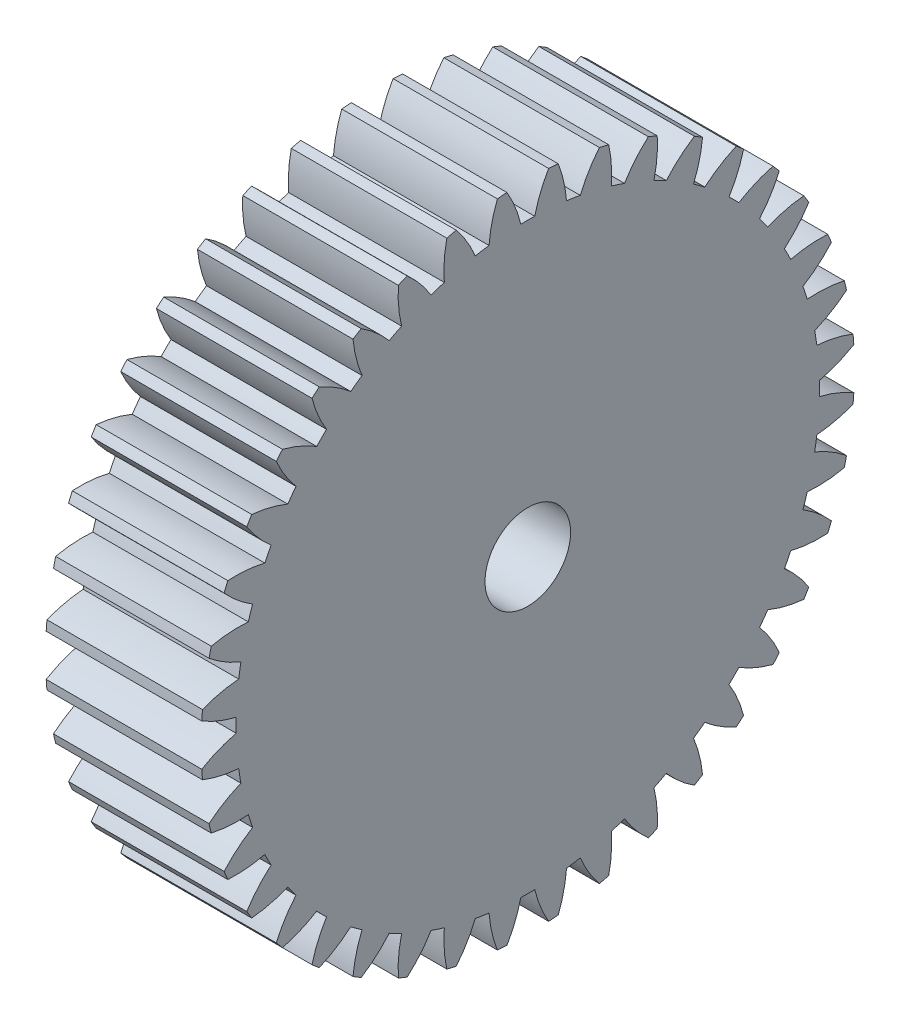
SolidWorks part; units mm, degrees
ref_plane "Front Plane" through (0, 0, 0) normal (0, 0, 1) x (1, 0, 0)
ref_plane "Top Plane" through (0, 0, 0) normal (0, 1, 0) x (1, 0, 0)
ref_plane "Right Plane" through (0, 0, 0) normal (1, 0, 0) x (0, 0, -1)
ref_plane "Plane1" through (-1.595, 0, 0) normal (1, 0, 0) x (0, 0, -1)
sketch "Sketch1" plane through (-1.595, 0, 0) normal (1, 0, 0) x (0, 0, -1)
  circle A0 centre (-8.0381, 6.9342) radius 0.4
  arc A1 (-16.421, 7.4699) -> (-15.535, 7.1132) centre (-14.7963, 10.2268) ccw
  arc A2 (-15.535, 7.1132) -> (-15.535, 6.7552) centre (-8.0381, 6.9342) ccw
  arc A3 (-15.535, 6.7552) -> (-16.421, 6.3985) centre (-14.7963, 3.6417) ccw
  arc A4 (-16.421, 6.3985) -> (-16.4016, 6.152) centre (-8.0381, 6.9342) ccw
  arc A5 (-16.4016, 6.152) -> (-15.4707, 5.9382) centre (-15.2282, 9.129) ccw
  arc A6 (-15.4707, 5.9382) -> (-15.4147, 5.5847) centre (-8.0381, 6.9342) ccw
  arc A7 (-15.4147, 5.5847) -> (-16.234, 5.0937) centre (-14.198, 2.625) ccw
  arc A8 (-16.234, 5.0937) -> (-16.1763, 4.8533) centre (-8.0381, 6.9342) ccw
  arc A9 (-16.1763, 4.8533) -> (-15.2234, 4.7878) centre (-15.483, 7.9773) ccw
  arc A10 (-15.2234, 4.7878) -> (-15.1128, 4.4473) centre (-8.0381, 6.9342) ccw
  arc A11 (-15.1128, 4.4473) -> (-15.8452, 3.8343) centre (-13.4481, 1.7144) ccw
  arc A12 (-15.8452, 3.8343) -> (-15.7506, 3.6058) centre (-8.0381, 6.9342) ccw
  arc A13 (-15.7506, 3.6058) -> (-14.7992, 3.6902) centre (-15.5545, 6.7998) ccw
  arc A14 (-14.7992, 3.6902) -> (-14.6366, 3.3712) centre (-8.0381, 6.9342) ccw
  arc A15 (-14.6366, 3.3712) -> (-15.2641, 2.6511) centre (-12.5649, 0.9324) ccw
  arc A16 (-15.2641, 2.6511) -> (-15.1349, 2.4403) centre (-8.0381, 6.9342) ccw
  arc A17 (-15.1349, 2.4403) -> (-14.2084, 2.6725) centre (-15.4409, 5.6256) ccw
  arc A18 (-14.2084, 2.6725) -> (-13.998, 2.3829) centre (-8.0381, 6.9342) ccw
  arc A19 (-13.998, 2.3829) -> (-14.5052, 1.5735) centre (-11.5703, 0.2981) ccw
  arc A20 (-14.5052, 1.5735) -> (-14.3446, 1.3854) centre (-8.0381, 6.9342) ccw
  arc A21 (-14.3446, 1.3854) -> (-13.4658, 1.7597) centre (-15.1451, 4.4837) ccw
  arc A22 (-13.4658, 1.7597) -> (-13.2127, 1.5066) centre (-8.0381, 6.9342) ccw
  arc A23 (-13.2127, 1.5066) -> (-13.5869, 0.6278) centre (-10.4887, -0.1727) ccw
  arc A24 (-13.5869, 0.6278) -> (-13.3989, 0.4672) centre (-8.0381, 6.9342) ccw
  arc A25 (-13.3989, 0.4672) -> (-12.5895, 0.9743) centre (-14.6742, 3.4021) ccw
  arc A26 (-12.5895, 0.9743) -> (-12.2999, 0.7639) centre (-8.0381, 6.9342) ccw
  arc A27 (-12.2999, 0.7639) -> (-12.5321, -0.1626) centre (-9.3467, -0.4686) ccw
  arc A28 (-12.5321, -0.1626) -> (-12.3212, -0.2918) centre (-8.0381, 6.9342) ccw
  arc A29 (-12.3212, -0.2918) -> (-11.6011, 0.3357) centre (-14.04, 2.4075) ccw
  arc A30 (-11.6011, 0.3357) -> (-11.2822, 0.1732) centre (-8.0381, 6.9342) ccw
  arc A31 (-11.2822, 0.1732) -> (-11.3666, -0.7782) centre (-8.1726, -0.5821) ccw
  arc A32 (-11.3666, -0.7782) -> (-11.1381, -0.8728) centre (-8.0381, 6.9342) ccw
  arc A33 (-11.1381, -0.8728) -> (-10.525, -0.1404) centre (-13.2579, 1.5243) ccw
  arc A34 (-10.525, -0.1404) -> (-10.1846, -0.251) centre (-8.0381, 6.9342) ccw
  arc A35 (-10.1846, -0.251) -> (-10.1191, -1.2039) centre (-6.9951, -0.5106) ccw
  arc A36 (-10.1191, -1.2039) -> (-9.8786, -1.2617) centre (-8.0381, 6.9342) ccw
  arc A37 (-9.8786, -1.2617) -> (-9.3877, -0.4423) centre (-12.3474, 0.7744) ccw
  arc A38 (-9.3877, -0.4423) -> (-9.0341, -0.4984) centre (-8.0381, 6.9342) ccw
  arc A39 (-9.0341, -0.4984) -> (-8.8204, -1.4293) centre (-5.8433, -0.2558) ccw
  arc A40 (-8.8204, -1.4293) -> (-8.5739, -1.4487) centre (-8.0381, 6.9342) ccw
  arc A41 (-8.5739, -1.4487) -> (-8.2171, -0.5626) centre (-11.3307, 0.1761) ccw
  arc A42 (-8.2171, -0.5626) -> (-7.8591, -0.5626) centre (-8.0381, 6.9342) ccw
  arc A43 (-7.8591, -0.5626) -> (-7.5024, -1.4487) centre (-4.7456, 0.1761) ccw
  arc A44 (-7.5024, -1.4487) -> (-7.2559, -1.4293) centre (-8.0381, 6.9342) ccw
  arc A45 (-7.2559, -1.4293) -> (-7.0422, -0.4984) centre (-10.233, -0.2558) ccw
  arc A46 (-7.0422, -0.4984) -> (-6.6886, -0.4423) centre (-8.0381, 6.9342) ccw
  arc A47 (-6.6886, -0.4423) -> (-6.1976, -1.2617) centre (-3.7289, 0.7744) ccw
  arc A48 (-6.1976, -1.2617) -> (-5.9572, -1.2039) centre (-8.0381, 6.9342) ccw
  arc A49 (-5.9572, -1.2039) -> (-5.8917, -0.251) centre (-9.0812, -0.5106) ccw
  arc A50 (-5.8917, -0.251) -> (-5.5512, -0.1404) centre (-8.0381, 6.9342) ccw
  arc A51 (-5.5512, -0.1404) -> (-4.9382, -0.8728) centre (-2.8184, 1.5243) ccw
  arc A52 (-4.9382, -0.8728) -> (-4.7097, -0.7782) centre (-8.0381, 6.9342) ccw
  arc A53 (-4.7097, -0.7782) -> (-4.7941, 0.1732) centre (-7.9037, -0.5821) ccw
  arc A54 (-4.7941, 0.1732) -> (-4.4752, 0.3357) centre (-8.0381, 6.9342) ccw
  arc A55 (-4.4752, 0.3357) -> (-3.7551, -0.2918) centre (-2.0363, 2.4075) ccw
  arc A56 (-3.7551, -0.2918) -> (-3.5442, -0.1626) centre (-8.0381, 6.9342) ccw
  arc A57 (-3.5442, -0.1626) -> (-3.7764, 0.7639) centre (-6.7296, -0.4686) ccw
  arc A58 (-3.7764, 0.7639) -> (-3.4868, 0.9743) centre (-8.0381, 6.9342) ccw
  arc A59 (-3.4868, 0.9743) -> (-2.6774, 0.4672) centre (-1.4021, 3.4021) ccw
  arc A60 (-2.6774, 0.4672) -> (-2.4894, 0.6278) centre (-8.0381, 6.9342) ccw
  arc A61 (-2.4894, 0.6278) -> (-2.8636, 1.5066) centre (-5.5876, -0.1727) ccw
  arc A62 (-2.8636, 1.5066) -> (-2.6105, 1.7597) centre (-8.0381, 6.9342) ccw
  arc A63 (-2.6105, 1.7597) -> (-1.7317, 1.3854) centre (-0.9312, 4.4837) ccw
  arc A64 (-1.7317, 1.3854) -> (-1.5711, 1.5735) centre (-8.0381, 6.9342) ccw
  arc A65 (-1.5711, 1.5735) -> (-2.0783, 2.3829) centre (-4.506, 0.2981) ccw
  arc A66 (-2.0783, 2.3829) -> (-1.8678, 2.6725) centre (-8.0381, 6.9342) ccw
  arc A67 (-1.8678, 2.6725) -> (-0.9413, 2.4403) centre (-0.6354, 5.6256) ccw
  arc A68 (-0.9413, 2.4403) -> (-0.8121, 2.6511) centre (-8.0381, 6.9342) ccw
  arc A69 (-0.8121, 2.6511) -> (-1.4397, 3.3712) centre (-3.5114, 0.9324) ccw
  arc A70 (-1.4397, 3.3712) -> (-1.2771, 3.6902) centre (-8.0381, 6.9342) ccw
  arc A71 (-1.2771, 3.6902) -> (-0.3257, 3.6058) centre (-0.5218, 6.7998) ccw
  arc A72 (-0.3257, 3.6058) -> (-0.2311, 3.8343) centre (-8.0381, 6.9342) ccw
  arc A73 (-0.2311, 3.8343) -> (-0.9635, 4.4473) centre (-2.6282, 1.7144) ccw
  arc A74 (-0.9635, 4.4473) -> (-0.8529, 4.7878) centre (-8.0381, 6.9342) ccw
  arc A75 (-0.8529, 4.7878) -> (0.1, 4.8533) centre (-0.5933, 7.9773) ccw
  arc A76 (0.1, 4.8533) -> (0.1577, 5.0937) centre (-8.0381, 6.9342) ccw
  arc A77 (0.1577, 5.0937) -> (-0.6616, 5.5847) centre (-1.8783, 2.625) ccw
  arc A78 (-0.6616, 5.5847) -> (-0.6056, 5.9382) centre (-8.0381, 6.9342) ccw
  arc A79 (-0.6056, 5.9382) -> (0.3254, 6.152) centre (-0.8481, 9.129) ccw
  arc A80 (0.3254, 6.152) -> (0.3448, 6.3985) centre (-8.0381, 6.9342) ccw
  arc A81 (0.3448, 6.3985) -> (-0.5413, 6.7552) centre (-1.28, 3.6417) ccw
  arc A82 (-0.5413, 6.7552) -> (-0.5413, 7.1132) centre (-8.0381, 6.9342) ccw
  arc A83 (-0.5413, 7.1132) -> (0.3448, 7.4699) centre (-1.28, 10.2268) ccw
  arc A84 (0.3448, 7.4699) -> (0.3254, 7.7165) centre (-8.0381, 6.9342) ccw
  arc A85 (0.3254, 7.7165) -> (-0.6056, 7.9302) centre (-0.8481, 4.7394) ccw
  arc A86 (-0.6056, 7.9302) -> (-0.6616, 8.2838) centre (-8.0381, 6.9342) ccw
  arc A87 (-0.6616, 8.2838) -> (0.1577, 8.7747) centre (-1.8783, 11.2434) ccw
  arc A88 (0.1577, 8.7747) -> (0.1, 9.0152) centre (-8.0381, 6.9342) ccw
  arc A89 (0.1, 9.0152) -> (-0.8529, 9.0806) centre (-0.5933, 5.8912) ccw
  arc A90 (-0.8529, 9.0806) -> (-0.9635, 9.4211) centre (-8.0381, 6.9342) ccw
  arc A91 (-0.9635, 9.4211) -> (-0.2311, 10.0342) centre (-2.6282, 12.154) ccw
  arc A92 (-0.2311, 10.0342) -> (-0.3257, 10.2626) centre (-8.0381, 6.9342) ccw
  arc A93 (-0.3257, 10.2626) -> (-1.2771, 10.1782) centre (-0.5218, 7.0687) ccw
  arc A94 (-1.2771, 10.1782) -> (-1.4397, 10.4972) centre (-8.0381, 6.9342) ccw
  arc A95 (-1.4397, 10.4972) -> (-0.8121, 11.2173) centre (-3.5114, 12.936) ccw
  arc A96 (-0.8121, 11.2173) -> (-0.9413, 11.4281) centre (-8.0381, 6.9342) ccw
  arc A97 (-0.9413, 11.4281) -> (-1.8678, 11.1959) centre (-0.6354, 8.2428) ccw
  arc A98 (-1.8678, 11.1959) -> (-2.0783, 11.4856) centre (-8.0381, 6.9342) ccw
  arc A99 (-2.0783, 11.4856) -> (-1.5711, 12.295) centre (-4.506, 13.5703) ccw
  arc A100 (-1.5711, 12.295) -> (-1.7317, 12.483) centre (-8.0381, 6.9342) ccw
  arc A101 (-1.7317, 12.483) -> (-2.6105, 12.1087) centre (-0.9312, 9.3847) ccw
  arc A102 (-2.6105, 12.1087) -> (-2.8636, 12.3619) centre (-8.0381, 6.9342) ccw
  arc A103 (-2.8636, 12.3619) -> (-2.4894, 13.2406) centre (-5.5876, 14.0411) ccw
  arc A104 (-2.4894, 13.2406) -> (-2.6774, 13.4012) centre (-8.0381, 6.9342) ccw
  arc A105 (-2.6774, 13.4012) -> (-3.4868, 12.8941) centre (-1.4021, 10.4663) ccw
  arc A106 (-3.4868, 12.8941) -> (-3.7764, 13.1045) centre (-8.0381, 6.9342) ccw
  arc A107 (-3.7764, 13.1045) -> (-3.5442, 14.031) centre (-6.7296, 14.337) ccw
  arc A108 (-3.5442, 14.031) -> (-3.7551, 14.1602) centre (-8.0381, 6.9342) ccw
  arc A109 (-3.7551, 14.1602) -> (-4.4752, 13.5327) centre (-2.0363, 11.461) ccw
  arc A110 (-4.4752, 13.5327) -> (-4.7941, 13.6952) centre (-8.0381, 6.9342) ccw
  arc A111 (-4.7941, 13.6952) -> (-4.7097, 14.6466) centre (-7.9037, 14.4506) ccw
  arc A112 (-4.7097, 14.6466) -> (-4.9382, 14.7413) centre (-8.0381, 6.9342) ccw
  arc A113 (-4.9382, 14.7413) -> (-5.5512, 14.0088) centre (-2.8184, 12.3441) ccw
  arc A114 (-5.5512, 14.0088) -> (-5.8917, 14.1195) centre (-8.0381, 6.9342) ccw
  arc A115 (-5.8917, 14.1195) -> (-5.9572, 15.0724) centre (-9.0812, 14.379) ccw
  arc A116 (-5.9572, 15.0724) -> (-6.1976, 15.1301) centre (-8.0381, 6.9342) ccw
  arc A117 (-6.1976, 15.1301) -> (-6.6886, 14.3108) centre (-3.7289, 13.0941) ccw
  arc A118 (-6.6886, 14.3108) -> (-7.0422, 14.3668) centre (-8.0381, 6.9342) ccw
  arc A119 (-7.0422, 14.3668) -> (-7.2559, 15.2977) centre (-10.233, 14.1242) ccw
  arc A120 (-7.2559, 15.2977) -> (-7.5024, 15.3171) centre (-8.0381, 6.9342) ccw
  arc A121 (-7.5024, 15.3171) -> (-7.8591, 14.4311) centre (-4.7456, 13.6924) ccw
  arc A122 (-7.8591, 14.4311) -> (-8.2171, 14.4311) centre (-8.0381, 6.9342) ccw
  arc A123 (-8.2171, 14.4311) -> (-8.5739, 15.3171) centre (-11.3307, 13.6924) ccw
  arc A124 (-8.5739, 15.3171) -> (-8.8204, 15.2977) centre (-8.0381, 6.9342) ccw
  arc A125 (-8.8204, 15.2977) -> (-9.0341, 14.3668) centre (-5.8433, 14.1242) ccw
  arc A126 (-9.0341, 14.3668) -> (-9.3877, 14.3108) centre (-8.0381, 6.9342) ccw
  arc A127 (-9.3877, 14.3108) -> (-9.8786, 15.1301) centre (-12.3474, 13.0941) ccw
  arc A128 (-9.8786, 15.1301) -> (-10.1191, 15.0724) centre (-8.0381, 6.9342) ccw
  arc A129 (-10.1191, 15.0724) -> (-10.1846, 14.1195) centre (-6.9951, 14.379) ccw
  arc A130 (-10.1846, 14.1195) -> (-10.525, 14.0088) centre (-8.0381, 6.9342) ccw
  arc A131 (-10.525, 14.0088) -> (-11.1381, 14.7413) centre (-13.2579, 12.3441) ccw
  arc A132 (-11.1381, 14.7413) -> (-11.3666, 14.6466) centre (-8.0381, 6.9342) ccw
  arc A133 (-11.3666, 14.6466) -> (-11.2822, 13.6952) centre (-8.1726, 14.4506) ccw
  arc A134 (-11.2822, 13.6952) -> (-11.6011, 13.5327) centre (-8.0381, 6.9342) ccw
  arc A135 (-11.6011, 13.5327) -> (-12.3212, 14.1602) centre (-14.04, 11.461) ccw
  arc A136 (-12.3212, 14.1602) -> (-12.5321, 14.031) centre (-8.0381, 6.9342) ccw
  arc A137 (-12.5321, 14.031) -> (-12.2999, 13.1045) centre (-9.3467, 14.337) ccw
  arc A138 (-12.2999, 13.1045) -> (-12.5895, 12.8941) centre (-8.0381, 6.9342) ccw
  arc A139 (-12.5895, 12.8941) -> (-13.3989, 13.4012) centre (-14.6742, 10.4663) ccw
  arc A140 (-13.3989, 13.4012) -> (-13.5869, 13.2406) centre (-8.0381, 6.9342) ccw
  arc A141 (-13.5869, 13.2406) -> (-13.2127, 12.3619) centre (-10.4887, 14.0411) ccw
  arc A142 (-13.2127, 12.3619) -> (-13.4658, 12.1087) centre (-8.0381, 6.9342) ccw
  arc A143 (-13.4658, 12.1087) -> (-14.3446, 12.483) centre (-15.1451, 9.3847) ccw
  arc A144 (-14.3446, 12.483) -> (-14.5052, 12.295) centre (-8.0381, 6.9342) ccw
  arc A145 (-14.5052, 12.295) -> (-13.998, 11.4856) centre (-11.5703, 13.5703) ccw
  arc A146 (-13.998, 11.4856) -> (-14.2084, 11.1959) centre (-8.0381, 6.9342) ccw
  arc A147 (-14.2084, 11.1959) -> (-15.1349, 11.4281) centre (-15.4409, 8.2428) ccw
  arc A148 (-15.1349, 11.4281) -> (-15.2641, 11.2173) centre (-8.0381, 6.9342) ccw
  arc A149 (-15.2641, 11.2173) -> (-14.6366, 10.4972) centre (-12.5649, 12.936) ccw
  arc A150 (-14.6366, 10.4972) -> (-14.7992, 10.1782) centre (-8.0381, 6.9342) ccw
  arc A151 (-14.7992, 10.1782) -> (-15.7506, 10.2626) centre (-15.5545, 7.0687) ccw
  arc A152 (-15.7506, 10.2626) -> (-15.8452, 10.0342) centre (-8.0381, 6.9342) ccw
  arc A153 (-15.8452, 10.0342) -> (-15.1128, 9.4211) centre (-13.4481, 12.154) ccw
  arc A154 (-15.1128, 9.4211) -> (-15.2234, 9.0806) centre (-8.0381, 6.9342) ccw
  arc A155 (-15.2234, 9.0806) -> (-16.1763, 9.0152) centre (-15.483, 5.8912) ccw
  arc A156 (-16.1763, 9.0152) -> (-16.234, 8.7747) centre (-8.0381, 6.9342) ccw
  arc A157 (-16.234, 8.7747) -> (-15.4147, 8.2838) centre (-14.198, 11.2434) ccw
  arc A158 (-15.4147, 8.2838) -> (-15.4707, 7.9302) centre (-8.0381, 6.9342) ccw
  arc A159 (-15.4707, 7.9302) -> (-16.4016, 7.7165) centre (-15.2282, 4.7394) ccw
  arc A160 (-16.4016, 7.7165) -> (-16.421, 7.4699) centre (-8.0381, 6.9342) ccw
extrude "Boss-Extrude1" add sketch "Sketch1" against normal blind 4
sketch "Sketch2" plane through (-1.595, 0, 0) normal (1, 0, 0) x (0, 0, -1)
  circle A0 centre (-8.0381, 6.9342) radius 1.1
  dimension "D1" = 2.2
extrude "Cut-Extrude1" cut sketch "Sketch2" against normal through all
